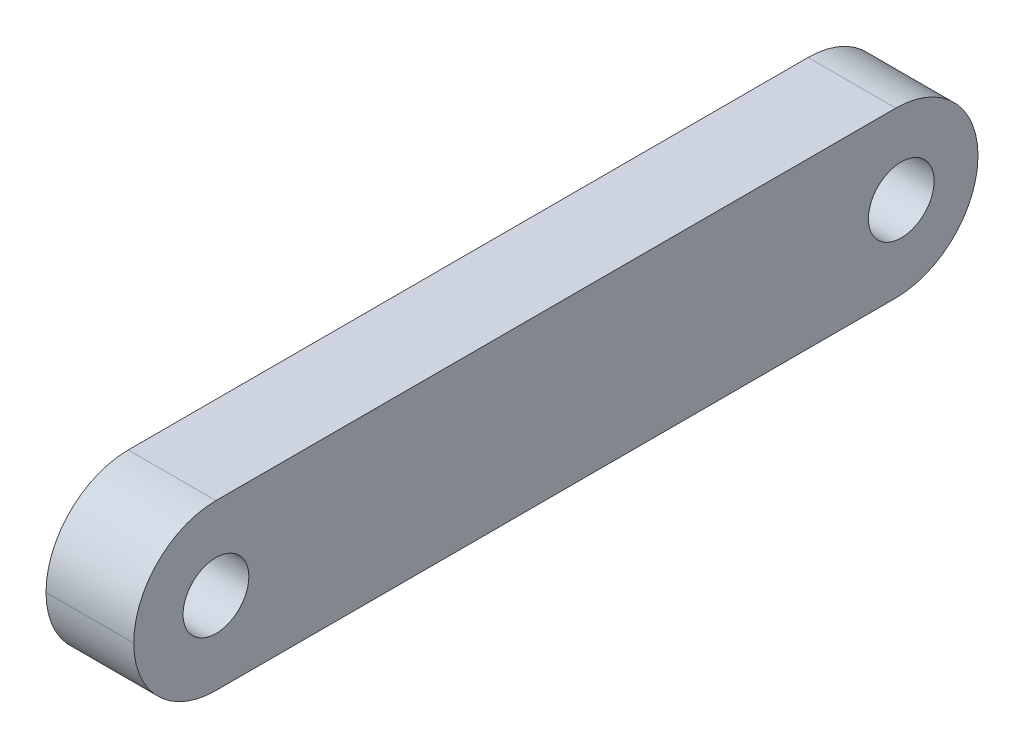
SolidWorks part; units mm, degrees
ref_plane "前视基准面" through (0, 0, 0) normal (0, 0, 1) x (1, 0, 0)
ref_plane "上视基准面" through (0, 0, 0) normal (0, 1, 0) x (1, 0, 0)
ref_plane "右视基准面" through (0, 0, 0) normal (1, 0, 0) x (0, 0, -1)
other "Configuration Table"
sketch "草图1" plane through (0, 0, 0) normal (1, 0, 0) x (0, 0, -1)
  line L5 (0, 0) -> (15.4, 0)
  line L6 (0, 0) -> (0, -3)
  line L7 (0, -3) -> (15.4, -3)
  line L8 (15.4, 0) -> (15.4, -3)
  circle A3 centre (1.5, -1.5) radius 0.6
  circle A4 centre (14, -1.5) radius 0.6
  point P9 (0, -1.5)
  dimension "D1" = 1.5
  dimension "D2" = 1.2
  dimension "D3" = 1.4
  dimension "D4" = 12.5
  dimension "D5" = 3
extrude "凸台-拉伸1" add sketch "草图1" along normal blind 1.6 contours L7 L8 L5 L6 | A3 | A4
fillet "圆角1" radius 1.5 4 edges at (0.8, -3, 0) (0.8, 0, 0) (0.8, -3, -15.4) (0.8, 0, -15.4)
